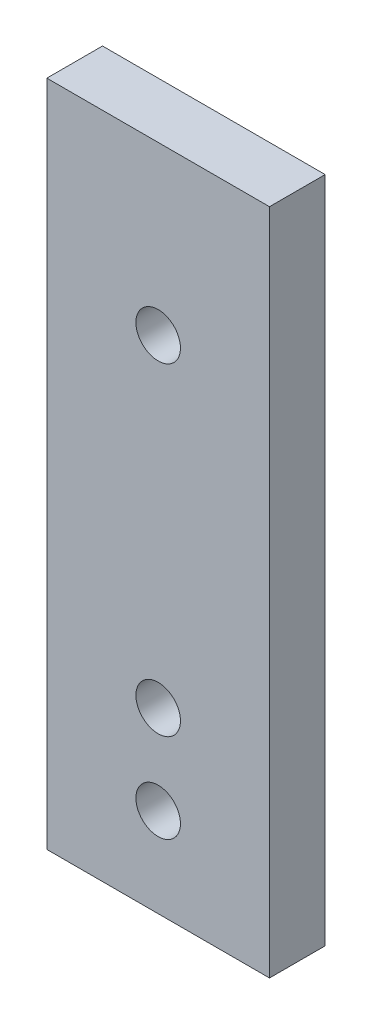
SolidWorks part; units mm, degrees
ref_plane "Front Plane" through (0, 0, 0) normal (0, 0, 1) x (1, 0, 0)
ref_plane "Top Plane" through (0, 0, 0) normal (0, 1, 0) x (1, 0, 0)
ref_plane "Right Plane" through (0, 0, 0) normal (1, 0, 0) x (0, 0, -1)
sketch "Sketch1" plane through (0, 0, 0) normal (0, 0, 1) x (1, 0, 0)
  line L0 (10, 60) -> (10, 0) construction
  line L1 (0, 0) -> (20, 0)
  line L2 (0, 0) -> (0, 60)
  line L3 (0, 60) -> (20, 60)
  line L4 (20, 0) -> (20, 60)
  line L5 (0, 45) -> (20, 45) construction
  line L6 (0, 8) -> (20, 8) construction
  line L7 (0, 16) -> (20, 16) construction
  circle A0 centre (10, 45) radius 2
  circle A1 centre (10, 16) radius 2
  circle A2 centre (10, 8) radius 2
  dimension "D4" = 4
  dimension "D1" = 20
  dimension "D2" = 60
  dimension "D3" = 15
  dimension "D5" = 8
  dimension "D6" = 8
extrude "Boss-Extrude1" add sketch "Sketch1" along normal blind 5
